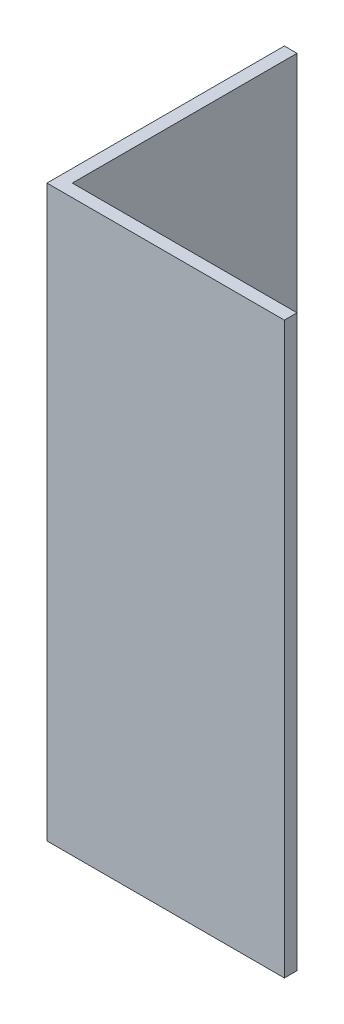
SolidWorks part; units mm, degrees
ref_plane "Спереди" through (0, 0, 0) normal (0, 0, 1) x (1, 0, 0)
ref_plane "Сверху" through (0, 0, 0) normal (0, 1, 0) x (1, 0, 0)
ref_plane "Справа" through (0, 0, 0) normal (1, 0, 0) x (0, 0, -1)
sketch "Эскиз1" plane through (0, 0, 0) normal (0, 1, 0) x (1, 0, 0)
  line L0 (0, 0) -> (75, 0)
  line L1 (0, 0) -> (0, 75)
extrude "Вытянуть-Тонкостенный1" add sketch "Эскиз1" along normal blind 180 thin thin type one direction wall 4
sketch "Эскиз6" plane through (0, 0, 0) normal (-1, 0, 0) x (0, 0, 1)
  circle A0 centre (-37.5, 25) radius 5
  circle A1 centre (-37.5, 75) radius 5
  circle A2 centre (-37.5, 125) radius 5
  dimension "D1" = 3
extrude "Вырез-Вытянуть1" cut sketch "Эскиз6" against normal blind 10
